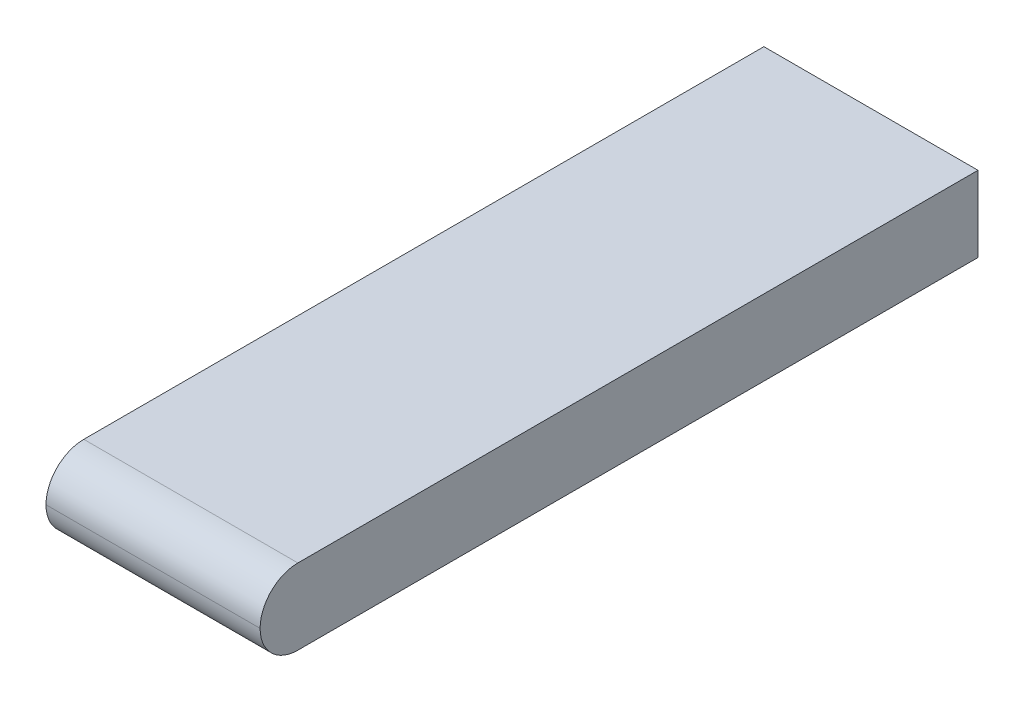
SolidWorks part; units mm, degrees
ref_plane "Front" through (0, 0, 0) normal (0, 0, 1) x (1, 0, 0)
ref_plane "Top" through (0, 0, 0) normal (0, 1, 0) x (1, 0, 0)
ref_plane "Right" through (0, 0, 0) normal (1, 0, 0) x (0, 0, -1)
sketch "Sketch1" plane through (0, 0, 0) normal (0, 1, 0) x (1, 0, 0)
  line L0 (-21.59, 72.39) -> (21.59, -72.39) construction
  line L1 (-21.59, 72.39) -> (21.59, 72.39)
  line L2 (-21.59, 72.39) -> (-21.59, -72.39)
  line L3 (-21.59, -72.39) -> (21.59, -72.39)
  line L4 (21.59, 72.39) -> (21.59, -72.39)
  dimension "D1" = 43.18
  dimension "D2" = 144.78
extrude "Boss-Extrude1" add sketch "Sketch1" along normal blind 15.24
fillet "Fillet1" radius 7.62 2 edges at (0, 0, 72.39) (0, 15.24, 72.39)
